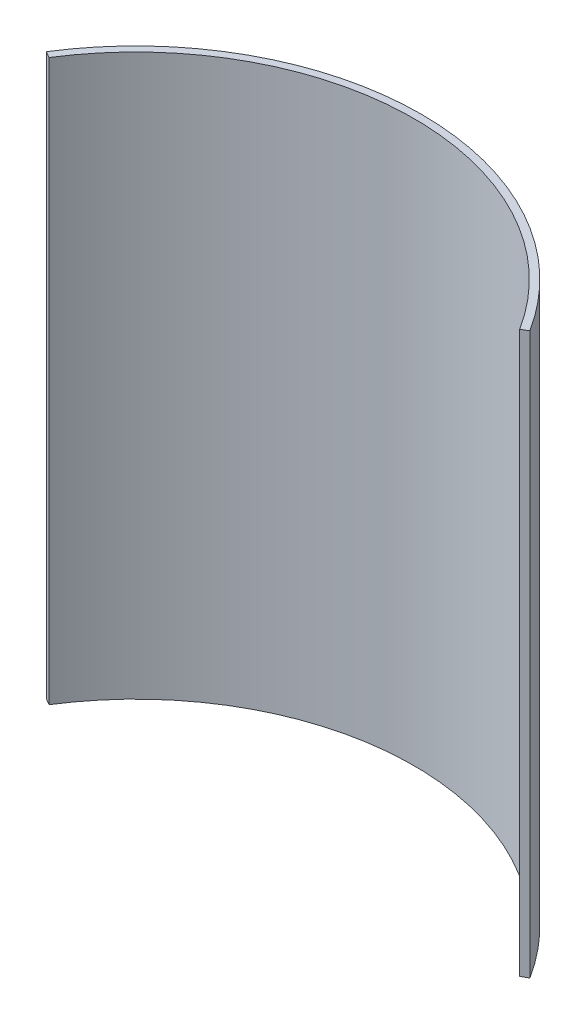
SolidWorks part; units mm, degrees
ref_plane "Front Plane" through (0, 0, 0) normal (0, 0, 1) x (1, 0, 0)
ref_plane "Top Plane" through (0, 0, 0) normal (0, 1, 0) x (1, 0, 0)
ref_plane "Right Plane" through (0, 0, 0) normal (1, 0, 0) x (0, 0, -1)
sketch "Sketch1" plane through (0, 0, 0) normal (0, 1, 0) x (1, 0, 0)
  line L0 (0, 45.7344) -> (0, 0) construction
  line L3 (-31.7, 20.034) -> (-32.5667, 20.5344)
  line L4 (39.6072, -22.8672) -> (0, 0) construction
  line L7 (-39.6072, -22.8672) -> (0, 0) construction
  line L8 (31.7, 20.034) -> (32.5667, 20.5344)
  arc A2 (32.5667, 20.5344) -> (-32.5667, 20.5344) centre (0, 0) ccw
  arc A3 (31.7, 20.034) -> (-31.7, 20.034) centre (0, 0) ccw
  dimension "D4" = 3
extrude "Boss-Extrude1" add sketch "Sketch1" against normal blind 75.5
